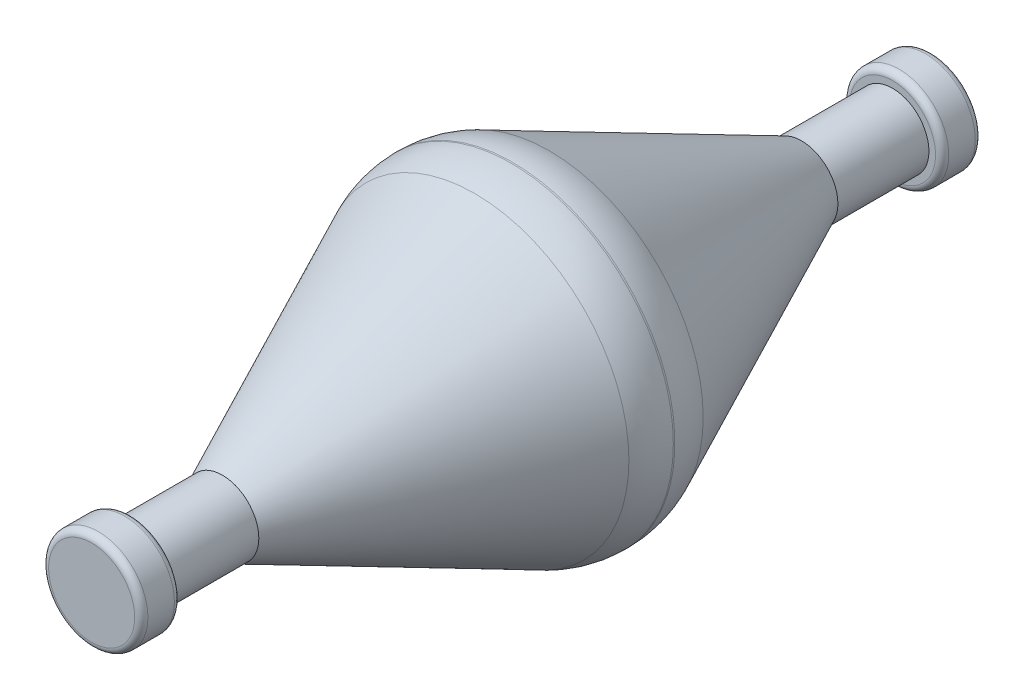
SolidWorks part; units mm, degrees
material "ABS"
ref_plane "Plan de face" through (0, 0, 0) normal (0, 0, 1) x (1, 0, 0)
ref_plane "Plan de dessus" through (0, 0, 0) normal (0, 1, 0) x (1, 0, 0)
ref_plane "Plan de droite" through (0, 0, 0) normal (1, 0, 0) x (0, 0, -1)
sketch "Esquisse1" plane through (0, 0, 0) normal (0, 0, 1) x (1, 0, 0)
  circle A0 centre (0, 0) radius 6.125
  dimension "D1" = 12.25
extrude "Boss.-Extru.1" add sketch "Esquisse1" along normal blind 22
sketch "Esquisse2" plane through (0, 0, 22) normal (0, 0, 1) x (1, 0, 0)
  circle A0 centre (0, 0) radius 1.375
  dimension "D1" = 2.75
extrude "Boss.-Extru.2" add sketch "Esquisse2" along normal blind 15.875 and the other way blind 15.875 from offset 11 offset against normal yes
sketch "Esquisse3" plane through (0, 0, -4.875) normal (0, 0, -1) x (-1, 0, 0)
  circle A0 centre (0, 0) radius 1.875
  dimension "D1" = 3.75
extrude "Boss.-Extru.3" add sketch "Esquisse3" against normal blind 1.5
sketch "Esquisse4" plane through (0, 0, 26.875) normal (0, 0, 1) x (1, 0, 0)
  circle A0 centre (0, 0) radius 1.875
  dimension "D1" = 3.75
extrude "Boss.-Extru.4" add sketch "Esquisse4" against normal blind 1.5
chamfer "Chanfrein1" distance 10.25 angle 25 2 edges at (6.125, 0, 22) (6.125, 0, 0) first distance on face at (6.125, 0, 22)
fillet "Congé1" radius 3.25 2 edges at (6.125, 0, 11.75) (6.125, 0, 10.25)
fillet "Congé2" radius 0.25 4 edges at (-1.875, 0, -3.375) (-1.875, 0, -4.875) (1.875, 0, 25.375) (1.875, 0, 26.875)
